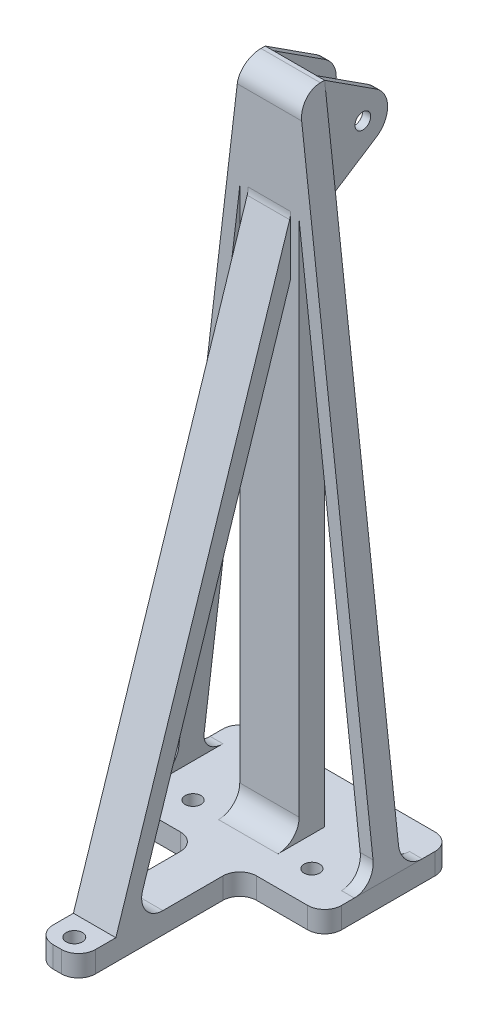
SolidWorks part; units mm, degrees
ref_plane "Front Plane" through (0, 0, 0) normal (0, 0, 1) x (1, 0, 0)
ref_plane "Top Plane" through (0, 0, 0) normal (0, 1, 0) x (1, 0, 0)
ref_plane "Right Plane" through (0, 0, 0) normal (1, 0, 0) x (0, 0, -1)
sketch "Sketch1" plane through (0, 0, 0) normal (0, 1, 0) x (1, 0, 0)
  line L0 (0, 15) -> (0, -15) construction
  line L1 (-25, -15) -> (25, -15)
  line L2 (-25, -15) -> (-25, 15)
  line L3 (-25, 15) -> (25, 15)
  line L4 (25, -15) -> (25, 15)
  line L5 (-25, -15) -> (25, 15) construction
  line L6 (-25, 15) -> (25, -15) construction
  line L7 (0, 0) -> (25, 0) construction
  circle A2 centre (0, 7) radius 1.85
  circle A3 centre (14, 7) radius 1.85
  circle A4 centre (-14, 7) radius 1.85
  circle A5 centre (14, -7) radius 1.85
  circle A6 centre (0, -7) radius 1.85
  circle A7 centre (-14, -7) radius 1.85
  point P0 (0, 0)
  dimension "D3" = 14
  dimension "D4" = 14
  dimension "D6" = 3.7
  dimension "D1" = 50
  dimension "D2" = 30
  dimension "D5" = 7
extrude "Boss-Extrude1" add sketch "Sketch1" along normal blind 5
ref_plane "Plane1" through (0, 0, 0) normal (0, 0, 1) x (1, 0, 0)
sketch "Sketch3" plane through (0, 0, 0) normal (0, 0, 1) x (1, 0, 0)
  line L0 (-25, 5) -> (-7, 157.4)
  line L1 (0, 5) -> (0, 157.4) construction
  line L2 (-25, 5) -> (25, 5) construction
  line L3 (-7, 5) -> (-7, 157.4)
  line L4 (-21.9791, 5) -> (-7, 131.8234)
  line L5 (21.9791, 5) -> (7, 131.8234)
  line L6 (-25, 5) -> (-7, 5)
  line L7 (25, 5) -> (7, 157.4)
  line L8 (7, 5) -> (7, 157.4)
  line L9 (25, 5) -> (7, 5)
  line L10 (-7, 157.4) -> (7, 157.4)
  line L11 (-7, 5) -> (7, 5)
  dimension "D1" = 7
  dimension "D2" = 152.4
  dimension "D3" = 3
extrude "Boss-Extrude2" add sketch "Sketch3" along normal blind 3 and the other way blind 3 contours L0 L6 L4 L3 | L9 L7 L8 L5 | L11 L1 L10 L3 | L1 L11 L8 L10
ref_plane "Plane2" through (0, 0, 0) normal (1, 0, 0) x (0, 0, -1)
sketch "Sketch4" plane through (0, 0, 0) normal (1, 0, 0) x (0, 0, -1)
  line L0 (3, 131.8234) -> (-3, 131.8234) construction
  line L1 (3, 131.8234) -> (-3, 131.8234)
  line L2 (3, 157.4) -> (-3, 157.4) construction
  line L3 (3, 157.4) -> (-3, 157.4)
  line L4 (0, 157.4) -> (0, 131.8234) construction
  line L5 (0, 144.6117) -> (12, 144.6117) construction
  line L6 (3, 157.4) -> (15.1771, 149.5238)
  line L7 (3, 131.8234) -> (15.1771, 139.6997)
  line L8 (3, 157.4) -> (3, 131.8234)
  circle A0 centre (12, 144.6117) radius 1.85
  arc A1 (15.1771, 139.6997) -> (15.1771, 149.5238) centre (12, 144.6117) ccw
  circle A2 centre (12, 144.6117) radius 5.85 construction
  dimension "D1" = 3.7
  dimension "D3" = 12
  dimension "D2" = 4
extrude "Boss-Extrude3" add sketch "Sketch4" along normal up to vertex (2.5 mm away) contours L7 A1 L6 L8 A0
mirror "Mirror1" about plane through (0, 0, 0) normal (1, 0, 0) of "Boss-Extrude3"
sketch "Sketch6" plane through (0, 157.4, 0) normal (0, 1, 0) x (1, 0, 0)
  line L0 (-7, 3) -> (7, 3) construction
  line L1 (5.1, 3) -> (-5.1, 3)
  line L2 (5.1, 3) -> (5.1, 17.85)
  line L3 (5.1, 17.85) -> (-5.1, 17.85)
  line L4 (-5.1, 3) -> (-5.1, 17.85)
  line L5 (7, 17.85) -> (-7, 17.85) construction
  line L6 (0, -2.75) -> (0, 2.75) construction
  point P8 (0, 17.85)
  dimension "D1" = 10.2
extrude "Cut-Extrude1" cut sketch "Sketch6" against normal up to surface (25.5766 mm away)
sketch "Sketch8" plane through (0, 0, 0) normal (0, -1, 0) x (1, 0, 0)
  line L0 (-25, 15) -> (25, 15) construction
  line L1 (-5, 15) -> (5, 15)
  line L2 (-5, 15) -> (-5, 53)
  line L3 (-5, 53) -> (5, 53)
  line L4 (5, 15) -> (5, 53)
  line L5 (0, -2.75) -> (0, 2.75) construction
  circle A0 centre (0, 7) radius 1.85 construction
  circle A1 centre (0, 7) radius 1.85
  circle A2 centre (0, 49) radius 1.917
  point P6 (0, 53)
  dimension "D1" = 38
  dimension "D2" = 10
  dimension "D3" = 42
extrude "Boss-Extrude4" add sketch "Sketch8" against normal up to surface (5 mm away) up to face at (0, 5, 0)
sketch "Sketch9" plane through (0, 0, 0) normal (1, 0, 0) x (0, 0, -1)
  line L0 (-53, 5) -> (-15, 5) construction
  line L1 (-53, 5) -> (-15, 5)
  line L2 (-44.2058, 5) -> (-3, 131.8234)
  line L3 (-40, 5) -> (-3, 118.8787)
  line L4 (3, 131.8234) -> (-3, 131.8234)
  line L5 (-3, 131.8234) -> (-3, 5)
  line L6 (-3, 5) -> (3, 5)
  line L7 (3, 5) -> (3, 131.8234)
  line L8 (3, 131.8234) -> (-3, 131.8234)
  line L9 (-3, 131.8234) -> (-3, 5)
  line L10 (-3, 5) -> (3, 5)
  line L11 (3, 5) -> (3, 131.8234)
  line L12 (-40, 5) -> (-44.2058, 5)
  line L13 (-44.2058, 5) -> (-3, 131.8234)
  dimension "D2" = 4
  dimension "D3" = 37
  dimension "D1" = 0
extrude "Boss-Extrude5" add sketch "Sketch9" along normal up to surface and the other way up to surface contours L9 L2 L1 L3 up to face at (5, 2.5, 34) other way up to face at (-5, 2.5, 34)
fillet "Fillet1" radius 5 7 edges at (23.4896, 5, -3) (23.4896, 5, 3) (-23.4896, 5, 3) (0, 5, 3) (0, 5, 40) (0, 131.8234, 3) (0, 157.4, 3)
fillet "Fillet2" radius 4 8 edges at (-25, 2.5, -15) (25, 2.5, -15) (25, 2.5, 15) (5, 2.5, 15) (5, 2.5, 53) (-5, 2.5, 53) (-25, 2.5, 15) (-5, 2.5, 15)
